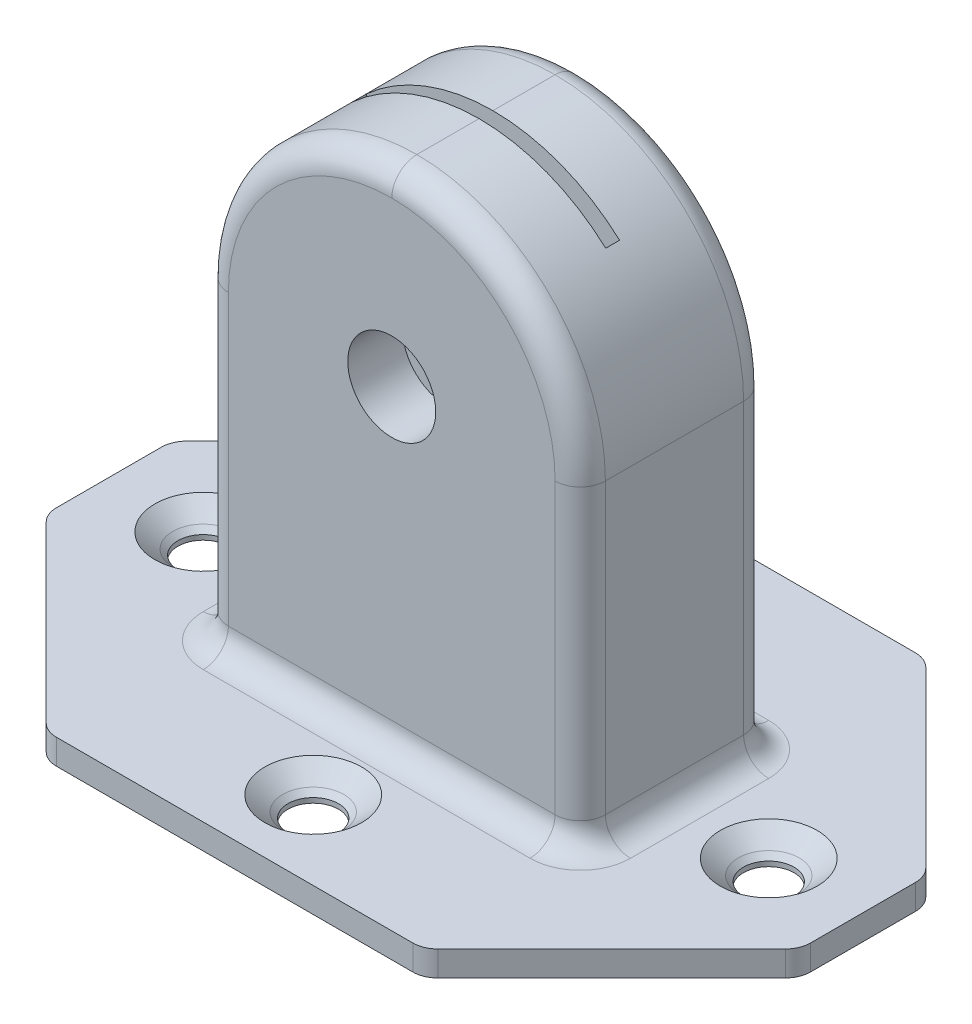
SolidWorks part; units mm, degrees
ref_plane "Front Plane" through (0, 0, 0) normal (0, 0, 1) x (1, 0, 0)
ref_plane "Top Plane" through (0, 0, 0) normal (0, 1, 0) x (1, 0, 0)
ref_plane "Right Plane" through (0, 0, 0) normal (1, 0, 0) x (0, 0, -1)
sketch "Main_Base_Dim" plane through (0, 0, 0) normal (0, 1, 0) x (1, 0, 0)
  line L1 (0, 0) -> (76.2, 0)
  line L2 (0, 0) -> (0, 50.8)
  line L3 (0, 50.8) -> (76.2, 50.8)
  line L4 (76.2, 0) -> (76.2, 50.8)
  dimension "D1" = 76.2
  dimension "D2" = 50.8
extrude "Main_Base" add sketch "Main_Base_Dim" along normal blind 2.54
sketch "Linkage_Holder_Dim" plane through (0, 2.54, 0) normal (0, 1, 0) x (1, 0, 0)
  line L0 (0, 50.8) -> (0, 0) construction
  line L1 (19.05, 34.925) -> (57.15, 34.925)
  line L2 (19.05, 34.925) -> (19.05, 15.875)
  line L3 (19.05, 15.875) -> (57.15, 15.875)
  line L4 (57.15, 34.925) -> (57.15, 15.875)
  line L5 (76.2, 50.8) -> (0, 50.8) construction
  point P6 (0, 25.4)
  point P7 (19.05, 25.4)
  point P10 (38.1, 50.8)
  point P11 (38.1, 34.925)
  dimension "D1" = 38.1
  dimension "D3" = 19.05
extrude "Linkage_Holder" add sketch "Linkage_Holder_Dim" along normal blind 50.8
sketch "Linkage_Slot_Dim" plane through (0, 53.34, 0) normal (0, 1, 0) x (1, 0, 0)
  line L0 (57.15, 34.925) -> (19.05, 34.925) construction
  line L1 (25.3, 26.1) -> (50.9, 26.1)
  line L2 (25.3, 26.1) -> (25.3, 24.7)
  line L3 (25.3, 24.7) -> (50.9, 24.7)
  line L4 (50.9, 26.1) -> (50.9, 24.7)
  line L5 (19.05, 34.925) -> (19.05, 15.875) construction
  point P6 (38.1, 34.925)
  point P7 (38.1, 26.1)
  point P10 (19.05, 25.4)
  point P11 (25.3, 25.4)
  dimension "D1" = 25.6
  dimension "D2" = 1.4
extrude "Linkage_Slot" cut sketch "Linkage_Slot_Dim" against normal blind 50.8
fillet ".75in_Fillet" radius 19.05 2 edges at (57.15, 53.34, -25.4) (19.05, 53.34, -25.4)
sketch "Bolt_Hole_Dim" plane through (0, 0, -15.875) normal (0, 0, 1) x (1, 0, 0)
  line L0 (38.1, 53.34) -> (38.1, 2.54) construction
  line L1 (19.05, 2.54) -> (57.15, 2.54) construction
  line L2 (57.15, 34.29) -> (19.05, 34.29) construction
  circle A0 centre (38.1, 34.29) radius 2.1828
  dimension "D1" = 4.3656
extrude "Bolt_Hole" cut sketch "Bolt_Hole_Dim" against normal up to surface (19.05 mm away) up to face at (38.1, 26.9782, -34.925)
sketch "Bolt_Head_Dim" plane through (0, 0, -15.875) normal (0, 0, 1) x (1, 0, 0)
  circle A0 centre (38.1, 34.29) radius 4.445
  dimension "D1" = 8.89
extrude "Bolt_Head" cut sketch "Bolt_Head_Dim" against normal blind 5.5372
sketch "Nut_Slot_Dim" plane through (0, 0, -34.925) normal (0, 0, -1) x (-1, 0, 0)
  line L0 (0, 2.54) -> (-76.2, 2.54) construction
  line L1 (-35.6235, 38.5794) -> (-40.5765, 38.5794)
  line L2 (-40.5765, 38.5794) -> (-43.053, 34.29)
  line L3 (-43.053, 34.29) -> (-40.5765, 30.0006)
  line L4 (-40.5765, 30.0006) -> (-35.6235, 30.0006)
  line L5 (-35.6235, 30.0006) -> (-33.147, 34.29)
  line L6 (-33.147, 34.29) -> (-35.6235, 38.5794)
  circle A0 centre (-38.1, 34.29) radius 4.2894 construction
  dimension "D1" = 9.906
extrude "Nut_Slot" cut sketch "Nut_Slot_Dim" against normal blind 5.5372
sketch "Screw_Hole_Dim" plane through (0, 2.54, 0) normal (0, 1, 0) x (1, 0, 0)
  line L0 (19.05, 25.4) -> (0, 25.4) construction
  line L3 (0, 50.8) -> (0, 0) construction
  line L6 (19.05, 34.925) -> (19.05, 15.875) construction
  line L7 (57.15, 15.875) -> (57.15, 34.925) construction
  line L8 (19.05, 15.875) -> (57.15, 15.875) construction
  line L9 (38.1, 34.925) -> (38.1, 50.8) construction
  line L10 (57.15, 34.925) -> (19.05, 34.925) construction
  line L11 (76.2, 50.8) -> (0, 50.8) construction
  line L12 (57.15, 25.4) -> (76.2, 25.4) construction
  line L13 (76.2, 0) -> (76.2, 50.8) construction
  line L14 (38.1, 15.875) -> (38.1, 0) construction
  line L15 (0, 0) -> (76.2, 0) construction
  circle A0 centre (9.525, 25.4) radius 4.6
  circle A1 centre (38.1, 42.8625) radius 4.6
  circle A2 centre (66.675, 25.4) radius 4.6
  circle A3 centre (38.1, 7.9375) radius 4.6
  point P12 (19.05, 25.4)
  point P13 (38.1, 34.925)
  point P16 (57.15, 25.4)
  point P18 (38.1, 15.875)
  dimension "D1" = 9.2
hole_wizard "CSK for #10 Flat Head Machine Screw (100)1" positions "Sketch8" profile "Sketch9" countersink size "#10" standard "ANSI Inch" end condition through all
sketch "Sketch8" plane through (0, 2.54, 0) normal (0, 1, 0) x (1, 0, 0)
  point P0 (9.525, 25.4)
  point P3 (38.1, 42.8625)
  point P6 (66.675, 25.4)
  point P9 (38.1, 7.9375)
sketch "Sketch9" plane through (9.525, 2.54, -25.4) normal (1, 0, 0) x (0, 0, 1)
  line L0 (0, 0) -> (0, 2.54)
  line L1 (0, 2.54) -> (2.5527, 2.54)
  line L2 (2.5527, 2.54) -> (2.5527, 1.9608)
  line L3 (2.5527, 1.9608) -> (4.8895, 0)
  line L5 (4.8895, 0) -> (0, 0)
  line L6 (-2.5527, 1.9608) -> (-4.8895, 0) construction
  line L11 (0, -6.35) -> (0, 107.95) construction
  dimension "Thru Hole Dia." = 5.1054
  dimension "Thru Hole Depth" = 2.54
  dimension "Near C'Sink Dia." = 9.779
  dimension "Near C'Sink Angle" = 100
extrude "Screw_Hole" cut sketch "Screw_Hole_Dim" against normal blind 5.5372 draft 45
sketch "Corner_Cut_Dim" plane through (0, 2.54, 0) normal (0, 1, 0) x (1, 0, 0)
  line L0 (0, 0) -> (0, 19.05)
  line L1 (0, 50.8) -> (0, 0) construction
  line L2 (0, 19.05) -> (19.05, 0)
  line L3 (0, 0) -> (76.2, 0) construction
  line L4 (19.05, 0) -> (0, 0)
  line L5 (38.1, 50.8) -> (38.1, 0) construction
  line L6 (76.2, 50.8) -> (0, 50.8) construction
  line L7 (0, 25.4) -> (76.2, 25.4) construction
  line L8 (76.2, 0) -> (76.2, 50.8) construction
  line L9 (76.2, 0) -> (76.2, 19.05)
  line L10 (57.15, 0) -> (76.2, 0)
  line L11 (76.2, 19.05) -> (57.15, 0)
  line L12 (76.2, 50.8) -> (76.2, 31.75)
  line L13 (57.15, 50.8) -> (76.2, 50.8)
  line L14 (76.2, 31.75) -> (57.15, 50.8)
  line L15 (0, 31.75) -> (19.05, 50.8)
  line L16 (0, 50.8) -> (0, 31.75)
  line L17 (19.05, 50.8) -> (0, 50.8)
  dimension "D1" = 19.05
  dimension "D2" = 19.05
extrude "Corner_Cut" cut sketch "Corner_Cut_Dim" against normal up to surface (2.54 mm away) up to face at (9.525, 0, -22.8473)
fillet ".1in_Fillet" radius 2.54 20 edges at (38.1, 2.54, -34.925) (57.15, 2.54, -25.4) (19.05, 2.54, -25.4) (38.1, 2.54, -15.875) (57.15, 18.415, -34.925) (51.5704, 47.7604, -34.925) (24.6296, 47.7604, -34.925) (57.15, 18.415, -15.875) (51.5704, 47.7604, -15.875) (24.6296, 47.7604, -15.875) (19.05, 1.27, -50.8) (57.15, 1.27, -50.8) (76.2, 1.27, -31.75) (76.2, 1.27, -19.05) (57.15, 1.27, 0) (19.05, 1.27, 0) (0, 1.27, -19.05) (0, 1.27, -31.75) (19.05, 18.415, -34.925) (19.05, 18.415, -15.875)
